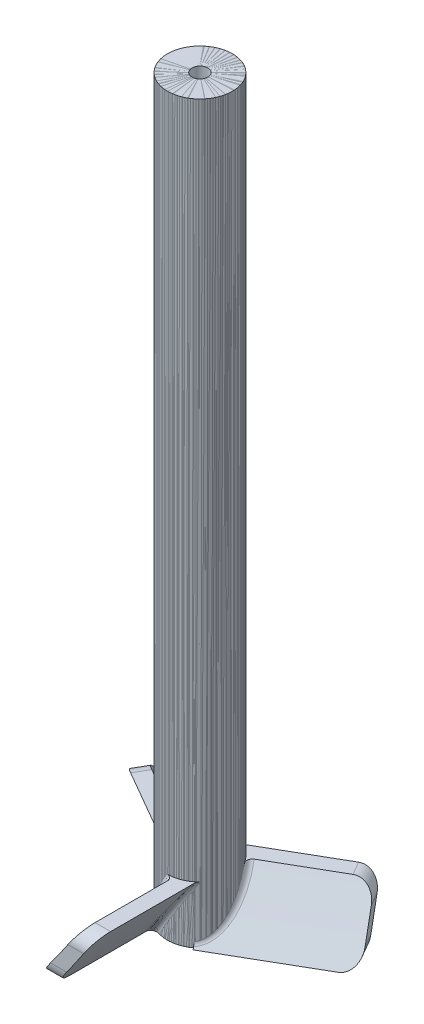
SolidWorks part; units mm, degrees
ref_plane "Front Plane" through (0, 0, 0) normal (0, 0, 1) x (1, 0, 0)
ref_plane "Top Plane" through (0, 0, 0) normal (0, 1, 0) x (1, 0, 0)
ref_plane "Right Plane" through (0, 0, 0) normal (1, 0, 0) x (0, 0, -1)
sketch "Sketch7" plane through (0, 0, 0) normal (0, 0, 1) x (1, 0, 0)
  line L0 (3.5176, 0) -> (-3.5176, 0) construction
  line L1 (6.849, 7) -> (4.9497, 7)
  line L2 (0, 0) -> (2, 0)
  arc A0 (0, 0) -> (4.9497, 7) centre (-91.3778, 69.8639) ccw
  arc A1 (6.849, 7) -> (2, 0) centre (-91.3778, 69.8639) cw
  dimension "D2" = 7
extrude "Boss-Extrude2" add sketch "Sketch7" along normal blind 15 contours A0 L1 A1 L2
fillet "Fillet1" radius 2 2 edges at (1, 0, 15) (5.8994, 7, 15)
sketch "Sketch10" plane through (0, 0, 0) normal (0, 1, 0) x (1, 0, 0)
  line L0 (0.3156, 0) -> (8.1957, 0) construction
  line L1 (4.9497, 0) -> (0, 0) construction
  line L2 (6.849, 0) -> (4.9497, 0) construction
  line L3 (2, 0) -> (6.849, 0) construction
  line L4 (4.2556, 0) -> (4.2556, 0.5251)
  line L5 (3.1481, -1000) -> (3.1481, 49000) construction
  circle A0 centre (4.2556, 0.5251) radius 3.9749
  point P5 (3.1481, 0)
  point P10 (-1.8519, 0)
  point P17 (3.1481, 0)
  dimension "D4" = 5
extrude "Boss-Extrude3" add sketch "Sketch10" along normal blind 90 contours A0 region at (0.3932, 0, -0.5251)
fillet "Fillet4" radius 0.7 2 edges at (1.2681, 1.6905, 2.0967) (3.7358, 2.3821, 3.4156)
pattern_circular "CirPattern1" count 3 over 360 about axis through (4.2556, 90, -0.5251) along (0, -1, 0) of bodies 103 102
sketch "Sketch11" plane through (0, 90, 0) normal (0, 1, 0) x (1, 0, 0)
  circle A3 centre (4.2556, 0.5251) radius 0.975
  circle A4 centre (4.2556, 0.5251) radius 3.9749 construction
  dimension "D1" = 1.95
extrude "Cut-Extrude1" cut sketch "Sketch11" against normal blind 40 contours A3
equation "\"insidebladediameter\"=0.01"
equation "\"height\"= 0.007"
equation "\"bladethickness\"=0.002"
equation "\"insidebladeradius\"= \"insidebladediameter\" / 2"
equation "\"D1@Sketch7\"=\"bladethickness\""
equation "\"D2@Sketch7\"=\"height\""
equation "\"bladewidth\"= \"height\" * cos ( \"bladeangle\" )"
equation "\"bladelength\"= 0.015"
equation "\"D1@Boss-Extrude2\"=\"bladelength\""
equation "\"bladetipradius\"= 0.002"
equation "\"D1@Fillet1\"=\"bladetipradius\""
equation "\"fusedistance\"= 0.0045"
equation "\"motorrodheight\"=0.09"
equation "\"D1@Boss-Extrude3\"=\"motorrodheight\""
equation "\"numberofblades\"= 3"
equation "\"D1@CirPattern1\"=\"numberofblades\""
equation "\"roddiameter\"= ( \"bladewidth\" + 0.003 )"
equation "\"roddepth\"= 0.005"
equation "\"bladeangle\"= 45deg"
equation "\"m\"=1"
equation "\"flatfacedist\"= 0.0005"
equation "\"motorshaftdiameter\"=0.002"
equation "\"D3@Sketch7\"=\"bladewidth\""
equation "\"D2@Sketch10\"=\"roddiameter\"/2-\"fusedistance\""
equation "\"D1@Sketch10\"=\"roddiameter\""
equation "\"bladefilletradius\"= 0.0007"
equation "\"D1@Fillet4\"=\"bladefilletradius\""
